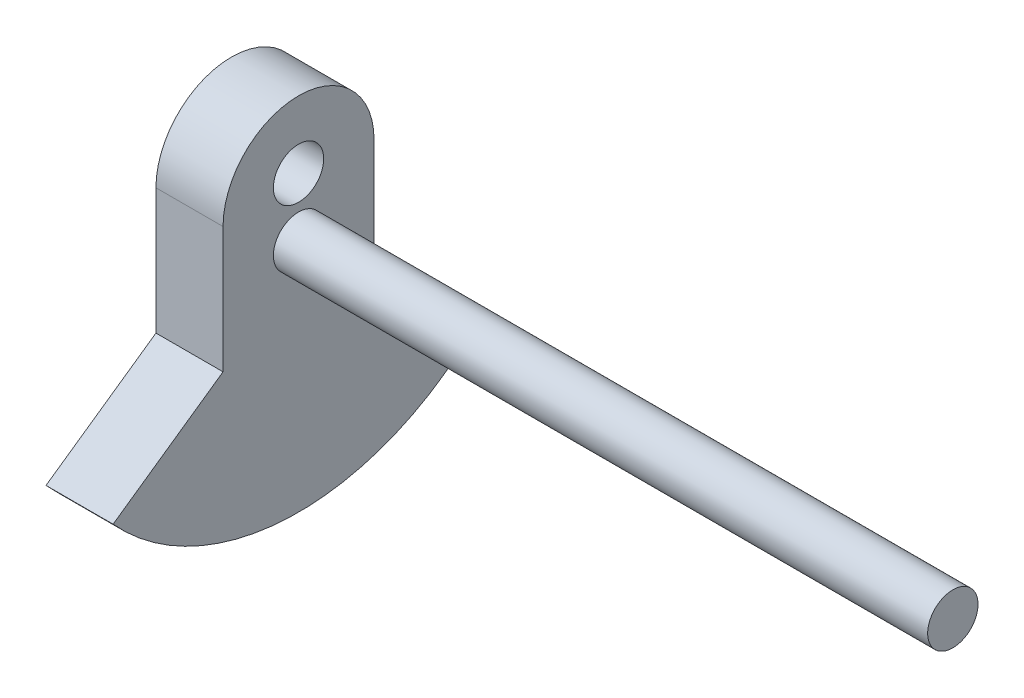
SolidWorks part; units mm, degrees
material "6061 Alloy"
ref_plane "Front Plane" through (0, 0, 0) normal (0, 0, 1) x (1, 0, 0)
ref_plane "Top Plane" through (0, 0, 0) normal (0, 1, 0) x (1, 0, 0)
ref_plane "Right Plane" through (0, 0, 0) normal (1, 0, 0) x (0, 0, -1)
sketch "Sketch1" plane through (0, 0, 0) normal (1, 0, 0) x (0, 0, -1)
  line L0 (0, 7.5) -> (0, 0) construction
  line L1 (0, 7.5) -> (0, -4.5) construction
  line L2 (-4.5, -4.5) -> (4.5, -4.5) construction
  line L3 (-4.5, -4.5) -> (-4.5, 3)
  line L4 (4.5, -4.5) -> (4.5, 3)
  line L5 (4.5, -4.5) -> (11.0532, -9.0886)
  line L6 (-4.5, -4.5) -> (-11.0532, -9.0886)
  line L7 (0, 7.5) -> (0, -14) construction
  arc A0 (-11.0532, -9.0886) -> (11.0532, -9.0886) centre (0, 0.8935) ccw
  circle A1 centre (0, 0) radius 1.5
  arc A2 (-4.5, 3) -> (4.5, 3) centre (0, 3) cw
  dimension "D2" = 3
  dimension "D1" = 7.5
  dimension "D3" = 12
  dimension "D4" = 9
  dimension "D5" = 125
  dimension "D6" = 8
  dimension "D7" = 21.5
extrude "Boss-Extrude1" add sketch "Sketch1" along normal blind 4
extrude "Boss-Extrude2" add sketch "Sketch1<2>" along normal blind 43 contours A1 region at (0, 0, 0)
sketch "Sketch1<2>" plane through (0, 0, 0) normal (1, 0, 0) x (0, 0, -1) same geometry as "Sketch1"
sketch "Sketch2" plane through (0, 0, 0) normal (-1, 0, 0) x (0, 0, 1)
  line L0 (0, 0) -> (0, 3.5) construction
  circle A0 centre (0, 3.5) radius 1.5
  arc A1 (4.5, 3) -> (-4.5, 3) centre (0, 3) ccw construction
  point P7 (0, 7.5)
  dimension "D2" = 3
  dimension "D1" = 4
extrude "Cut-Extrude1" cut sketch "Sketch2" against normal up to next
